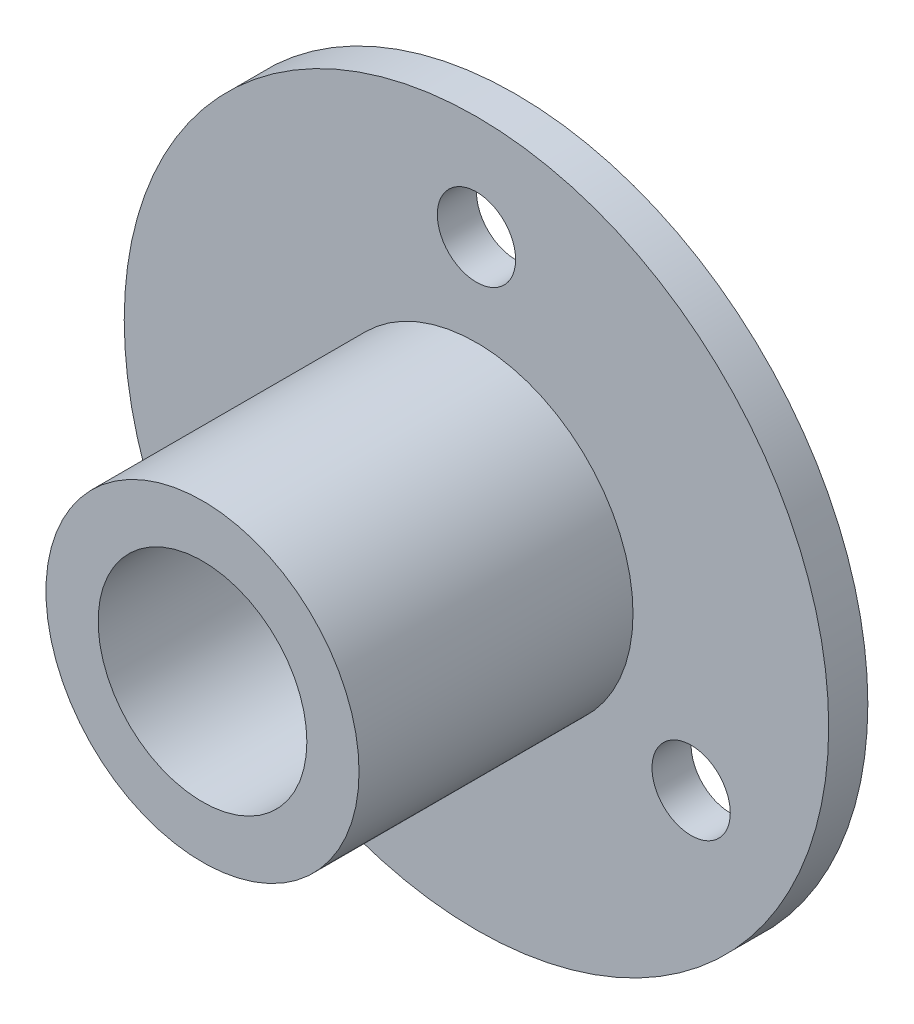
SolidWorks part; units mm, degrees
ref_plane "前视基准面" through (0, 0, 0) normal (0, 0, 1) x (1, 0, 0)
ref_plane "上视基准面" through (0, 0, 0) normal (0, 1, 0) x (1, 0, 0)
ref_plane "右视基准面" through (0, 0, 0) normal (1, 0, 0) x (0, 0, -1)
sketch "草图1" plane through (0, 0, 0) normal (0, 0, 1) x (1, 0, 0)
  line L0 (0, 0) -> (0, -20.1728) construction
  line L1 (31.3735, 0) -> (-21.8019, 0) construction
  line L2 (0, 0) -> (9.8733, -5.7004) construction
  line L3 (0, 0) -> (-10.0049, -5.7763) construction
  line L4 (8.3666, 4.5) -> (-8.3666, 4.5) construction
  line L5 (8.3666, 4.5) -> (8.3666, 10) construction
  line L6 (8.3666, 10) -> (-8.3666, 10) construction
  line L7 (-8.3666, 10) -> (-8.3666, 4.5) construction
  circle A0 centre (0, 0) radius 4
  circle A1 centre (0, 0) radius 13.5
  circle A2 centre (0, 0) radius 6
  circle A3 centre (0, 0) radius 9.5 construction
  circle A4 centre (8.2272, -4.75) radius 1.5
  circle A5 centre (-8.2272, -4.75) radius 1.5
  circle A6 centre (0, 9.5) radius 1.5
  point P15 (0, 0)
  dimension "D1" = 8
  dimension "D2" = 2
  dimension "D3" = 120
  dimension "D4" = 19
  dimension "D5" = 120
  dimension "D6" = 27
  dimension "D8" = 5.5
  dimension "D11" = 4.5
extrude "凸台-拉伸1" add sketch "草图1" along normal blind 1.5 contours A2 | A4 A2 region at (-13.1182, 0, 0) region at (-5.8303, 0, 0)
extrude "凸台-拉伸2" add sketch "草图1<4>" along normal blind 12 contours A2 A0 region at (-5.8303, 0, 0)
sketch "草图1<4>" plane through (0, 0, 0) normal (0, 0, 1) x (1, 0, 0) same geometry as "草图1"
